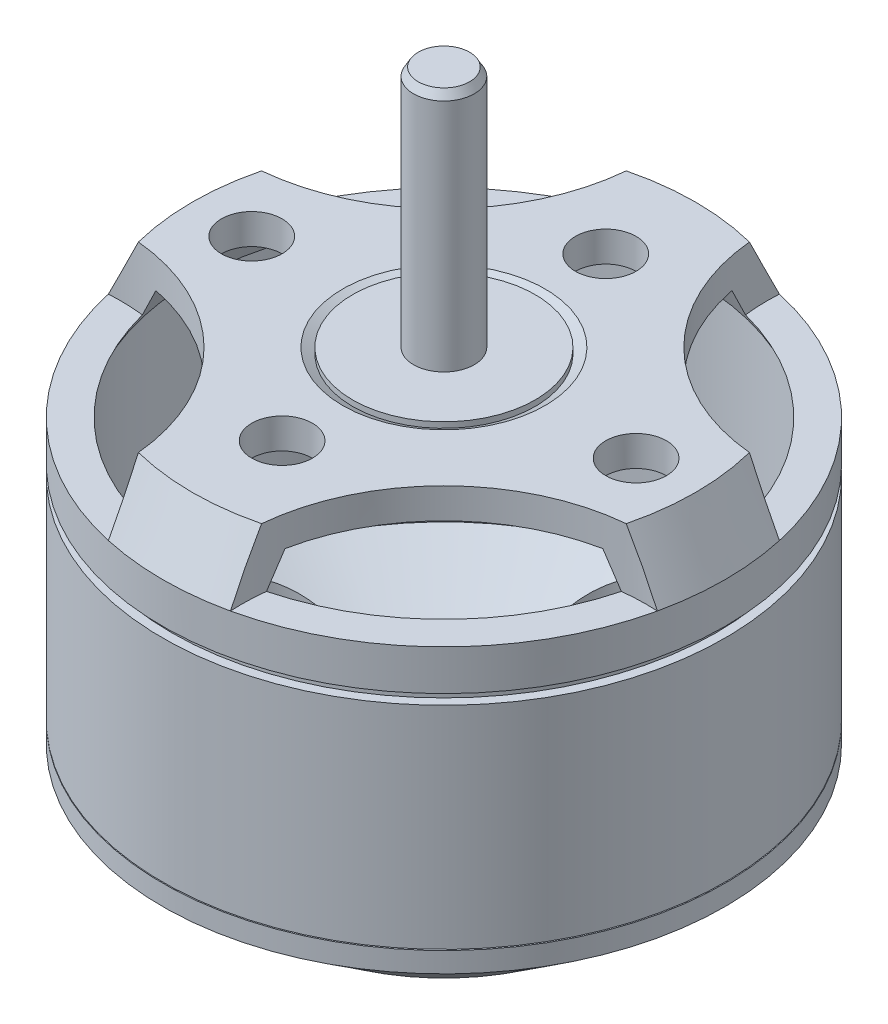
SolidWorks part; units mm, degrees
material "AISI 321 退火不锈钢 (SS)"
ref_plane "前视" through (0, 0, 0) normal (0, 0, 1) x (1, 0, 0)
ref_plane "上视" through (0, 0, 0) normal (0, 1, 0) x (1, 0, 0)
ref_plane "右视" through (0, 0, 0) normal (1, 0, 0) x (0, 0, -1)
sketch "草图1" plane through (0, 0, 0) normal (0, 1, 0) x (1, 0, 0)
  circle A0 centre (0, 0) radius 13.9
  dimension "D1" = 27.8
extrude "凸台-拉伸1" add sketch "草图1" along normal blind 21
chamfer "倒角1" distance 3 angle 26 1 edges at (0, 21, 13.9) first distance on face at (0, 21, 13.9)
chamfer "倒角3" distance 5.4 distance2 4 1 edges at (0, 0, 13.9) first distance on face at (0, 0, 13.9)
shell "抽壳1" thickness 1.5
sketch "草图2" plane through (0, 0, 0) normal (0, -1, 0) x (1, 0, 0)
  circle A0 centre (0, 0) radius 4.75
  dimension "D1" = 9.5
extrude "凸台-拉伸2" add sketch "草图2" along normal blind 2
sketch "草图4" plane through (0, -2, 0) normal (0, -1, 0) x (1, 0, 0)
  circle A0 centre (0, 0) radius 1.6
  dimension "D1" = 3.2
extrude "凸台-拉伸3" add sketch "草图4" along normal blind 0.3
sketch "草图5" plane through (0, 0, 0) normal (0, -1, 0) x (1, 0, 0)
  circle A0 centre (0, 8.5) radius 3.75
  dimension "D1" = 7.5
  dimension "D2" = 8.5
extrude "切除-拉伸1" cut sketch "草图5" against normal blind 7
pattern_circular "阵列(圆周)1" count 4 over 360 about axis through (0, 21, 0) along (0, -1, 0) of "切除-拉伸1"
sketch "草图6" plane through (0, 21, 0) normal (0, 1, 0) x (1, 0, 0)
  circle A0 centre (0, 8) radius 1.5
  circle A1 centre (-9.5, 0) radius 1.5
  dimension "D1" = 3
  dimension "D2" = 3
  dimension "D3" = 8
  dimension "D4" = 9.5
extrude "切除-拉伸2" cut sketch "草图6" against normal blind 5
pattern_circular "阵列(圆周)2" count 2 over 360 about axis through (0, 21, 0) along (0, -1, 0) of "切除-拉伸2"
sketch "草图7" plane through (0, 21, 0) normal (0, 1, 0) x (1, 0, 0)
  circle A0 centre (0, 0) radius 4
  dimension "D1" = 8
extrude "切除-拉伸3" cut sketch "草图7" against normal blind 1
chamfer "倒角4" distance 1 angle 30 1 edges at (0, 21, 4) first distance on face at (0, 21, 4)
sketch "草图8" plane through (0, 20, 0) normal (0, 1, 0) x (1, 0, 0)
  circle A0 centre (0, 0) radius 4.5123
extrude "凸台-拉伸4" add sketch "草图8" along normal blind 1
sketch "草图9" plane through (0, 21, 0) normal (0, 1, 0) x (1, 0, 0)
  circle A0 centre (0, 0) radius 1.5
  dimension "D1" = 3
extrude "凸台-拉伸5" add sketch "草图9" along normal blind 12
chamfer "倒角5" distance 0.4 angle 30 2 edges at (0, -2.3, -1.6) (0, 33, 1.5) first distance on face at (0, -2.3, -1.6) first distance on face at (0, 33, 1.5)
sketch "草图10" plane through (0, 0, 0) normal (0, 0, 1) x (1, 0, 0)
  line L0 (0, 33.8838) -> (0, -5.6036) construction
  line L1 (13.9, 18) -> (13.9, 2.4467) construction
  line L2 (13.9, 4) -> (13.9, 18) construction
  line L3 (12.4368, 21) -> (-12.4368, 21) construction
  line L4 (14.3469, 16) -> (13.4531, 16)
  line L5 (14.3469, 16) -> (14.3469, 15.5)
  line L6 (14.3469, 15.5) -> (13.4531, 15.5)
  line L7 (13.4531, 16) -> (13.4531, 15.5)
  line L8 (14.3469, 16) -> (13.4531, 15.5) construction
  line L9 (14.3469, 15.5) -> (13.4531, 16) construction
  line L10 (3.6576, 0) -> (7.6728, 0) construction
  line L11 (17.8258, 5) -> (9.9742, 5)
  line L12 (17.8258, 5) -> (17.8258, 5.05)
  line L13 (17.8258, 5.05) -> (9.9742, 5.05)
  line L14 (9.9742, 5) -> (9.9742, 5.05)
  line L15 (17.8258, 5) -> (9.9742, 5.05) construction
  line L16 (17.8258, 5.05) -> (9.9742, 5) construction
  point P7 (13.9, 15.75)
  point P14 (13.9, 5.025)
  dimension "D1" = 5
  dimension "D2" = 0.5
  dimension "D3" = 0.05
  dimension "D4" = 5
revolve "切除-旋转1" cut sketch "草图10" angle 360 about L0
sketch "草图11" plane through (0, 21, 0) normal (0, 1, 0) x (1, 0, 0)
  circle A0 centre (-13, 13) radius 10
  dimension "D1" = 20
  dimension "D2" = 13
  dimension "D3" = 13
extrude "切除-拉伸4" cut sketch "草图11" against normal blind 3
pattern_circular "阵列(圆周)3" count 4 over 360 about axis through (0, 21, 0) along (0, -1, 0) of "切除-拉伸4"
